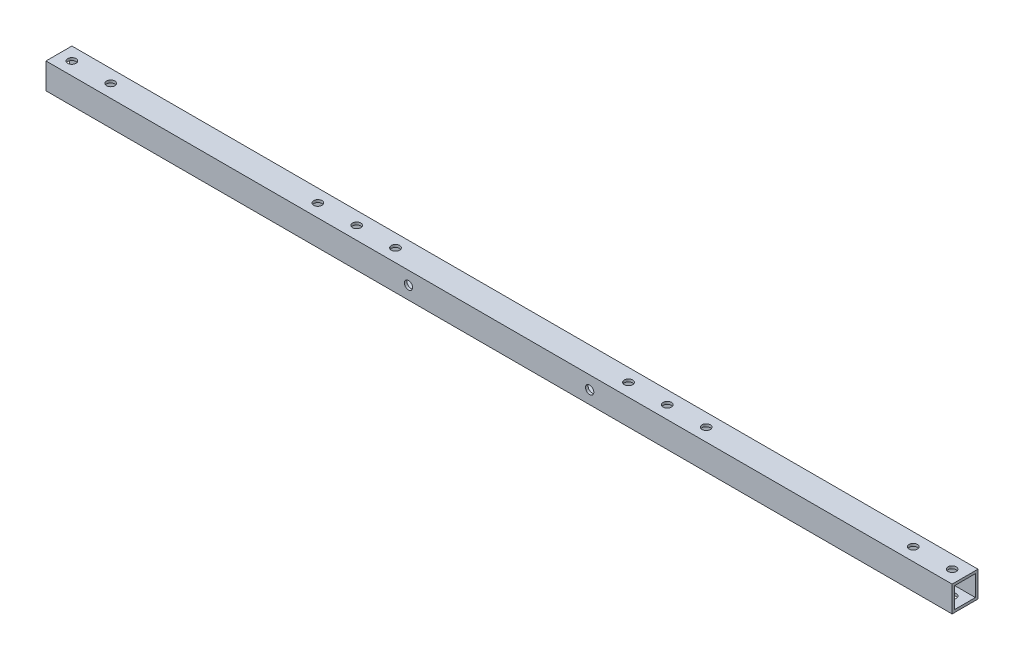
SolidWorks part; units mm, degrees
material "5052-O"
ref_plane "正面" through (0, 0, 0) normal (0, 0, 1) x (1, 0, 0)
ref_plane "平面" through (0, 0, 0) normal (0, 1, 0) x (1, 0, 0)
ref_plane "右側面" through (0, 0, 0) normal (1, 0, 0) x (0, 0, -1)
sketch "ｽｹｯﾁ1" plane through (0, 0, 0) normal (1, 0, 0) x (0, 0, -1)
  line L1 (-5, 5) -> (5, 5)
  line L2 (-5, 5) -> (-5, -5)
  line L3 (-5, -5) -> (5, -5)
  line L4 (5, 5) -> (5, -5)
  line L5 (-5, 5) -> (5, -5) construction
  line L6 (-5, -5) -> (5, 5) construction
  point P0 (0, 0)
  dimension "D1" = 10
  dimension "D2" = 10
extrude "ﾎﾞｽ - 押し出し1" add sketch "ｽｹｯﾁ1" along normal mid plane 350
sketch "ｽｹｯﾁ2" plane through (175, 0, 0) normal (1, 0, 0) x (0, 0, -1)
  line L0 (5, 5) -> (-5, 5) construction
  line L1 (-4, 4) -> (4, 4)
  line L2 (-4, 4) -> (-4, -4)
  line L3 (-4, -4) -> (4, -4)
  line L4 (4, 4) -> (4, -4)
  line L5 (-4, 4) -> (4, -4) construction
  line L6 (-4, -4) -> (4, 4) construction
  line L7 (5, -5) -> (5, 5) construction
  point P0 (0, 0)
  dimension "D1" = 1
  dimension "D2" = 1
extrude "ｶｯﾄ - 押し出し1" cut sketch "ｽｹｯﾁ2" against normal through all
sketch "ｽｹｯﾁ3" plane through (0, 5, 0) normal (0, 1, 0) x (1, 0, 0)
  line L0 (175, 5) -> (-175, 5) construction
  line L1 (-175, 5) -> (-175, -5) construction
  line L2 (0, -5.5) -> (0, 5.5) construction
  circle A0 centre (-170, 0) radius 1.6
  circle A1 centre (-155, 0) radius 1.6
  circle A2 centre (170, 0) radius 1.6
  circle A3 centre (155, 0) radius 1.6
  dimension "D1" = 3.2
  dimension "D2" = 5
  dimension "D3" = 5
  dimension "D4" = 2
extrude "ｶｯﾄ - 押し出し2" cut sketch "ｽｹｯﾁ3" against normal through all
sketch "ｽｹｯﾁ4" plane through (0, 5, 0) normal (0, 1, 0) x (1, 0, 0)
  line L0 (175, 5) -> (-175, 5) construction
  line L1 (-175, 5) -> (-175, -5) construction
  line L2 (0, -5.5) -> (0, 5.5) construction
  circle A0 centre (-75, 0) radius 1.6
  circle A1 centre (-60, 0) radius 1.6
  circle A2 centre (-45, 0) radius 1.6
  circle A3 centre (-75, 0) radius 1.6
  circle A4 centre (-60, 0) radius 1.6
  circle A6 centre (45, 0) radius 1.6
  circle A7 centre (60, 0) radius 1.6
  circle A8 centre (75, 0) radius 1.6
  circle A10 centre (-90, 0) radius 1.6 [skipped]
  dimension "D1" = 3.2
  dimension "D2" = 5
  dimension "D3" = 100
  dimension "D5" = 3
  dimension "D4" = 2
extrude "ｶｯﾄ - 押し出し3" cut sketch "ｽｹｯﾁ4" against normal through all contours A0 | A2 | A8 | A7 | A6 | A1 region at (-75, 5, 0) region at (-45, 5, 0) region at (45, 5, 0) region at (60, 5, 0) region at (75, 5, 0)
sketch "ｽｹｯﾁ5" plane through (0, 0, 5) normal (0, 0, 1) x (1, 0, 0)
  line L0 (175, 5) -> (-175, 5) construction
  line L1 (0, -5.5) -> (0, 5.5) construction
  circle A0 centre (-35, 0) radius 1.6
  circle A1 centre (35, 0) radius 1.6
  dimension "D1" = 3.2
  dimension "D2" = 5
  dimension "D3" = 35
extrude "ｶｯﾄ - 押し出し4" cut sketch "ｽｹｯﾁ5" against normal through all
